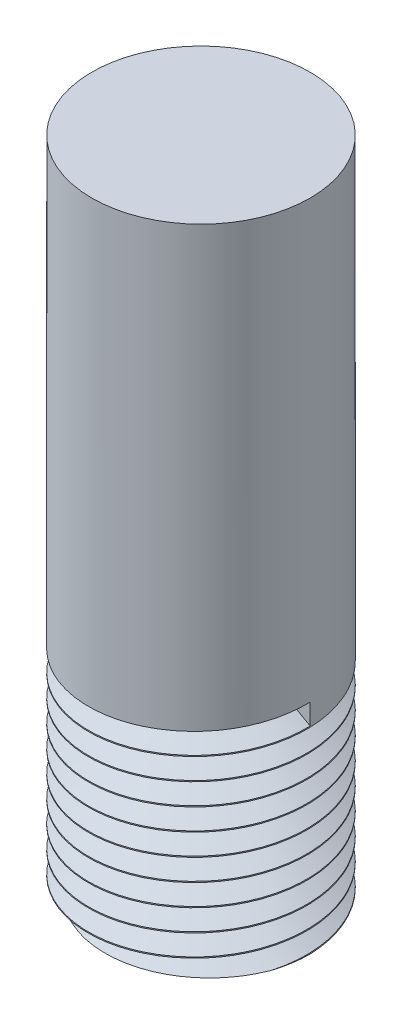
SolidWorks part; units mm, degrees
ref_plane "Front Plane" through (0, 0, 0) normal (0, 0, 1) x (1, 0, 0)
ref_plane "Top Plane" through (0, 0, 0) normal (0, 1, 0) x (1, 0, 0)
ref_plane "Right Plane" through (0, 0, 0) normal (1, 0, 0) x (0, 0, -1)
sketch "Sketch1" plane through (0, 0, 0) normal (0, 1, 0) x (1, 0, 0)
  circle A0 centre (0, 0) radius 5
  dimension "D1" = 10
extrude "Boss-Extrude1" add sketch "Sketch1" along normal blind 30
sketch "Sketch2" plane through (0, 0, 0) normal (0, 1, 0) x (1, 0, 0)
  circle A0 centre (0, 0) radius 5
  dimension "D1" = 10
curve "Helix/Spiral1" pitch 1 height 10 radius 5 centre (0, 0, 0) axis (0, 1, 0) start towards (1, 0, 0)
sketch "Sketch3" plane through (0, 0, 0) normal (0, 0, 1) x (1, 0, 0)
  line L1 (5, -0.95) -> (5, 0)
  line L2 (5, 0) -> (4.1773, -0.475)
  line L3 (4.1773, -0.475) -> (5, -0.95)
  circle A0 centre (4.7258, -0.475) radius 0.2742 construction
  point P1 (4.5354, -0.7158)
  point P6 (0, 0)
  dimension "D1" = 0.95
sweep "Cut-Sweep1" cut profiles "Sketch3" path "Helix/Spiral1" align with end faces yes
